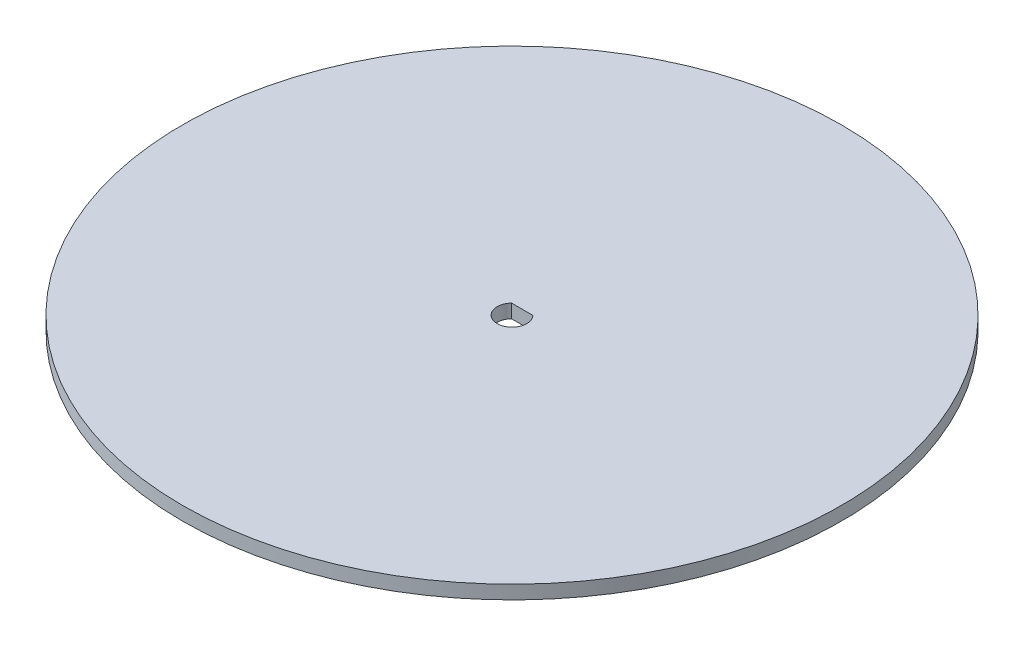
SolidWorks part; units mm, degrees
ref_plane "Front Plane" through (0, 0, 0) normal (0, 0, 1) x (1, 0, 0)
ref_plane "Top Plane" through (0, 0, 0) normal (0, 1, 0) x (1, 0, 0)
ref_plane "Right Plane" through (0, 0, 0) normal (1, 0, 0) x (0, 0, -1)
sketch "Sketch1" plane through (0, 0, 0) normal (0, 1, 0) x (1, 0, 0)
  circle A0 centre (0, 0) radius 72.5
  dimension "D1" = 145
base flange "Base-Flange1" sketch "Sketch1" thickness 3 reverse thickness direction no parameters "D1"=0.7366
sketch "Sketch6" plane through (0, 0, 0) normal (0, 1, 0) x (1, 0, 0)
  line L0 (-2.3452, 2.25) -> (2.3452, 2.25)
  circle A0 centre (0, 0) radius 3.25 construction
  arc A1 (-2.3452, 2.25) -> (2.3452, 2.25) centre (0, 0) ccw
  point P5 (0, -3.25)
  dimension "D1" = 6.5
  dimension "D2" = 5.5
extrude "Cut-Extrude1" cut sketch "Sketch6" against normal up to next normal cut yes
sketch "Bend-Lines1" [suppressed] plane through (0, 0, 0) normal (0, 1, 0) x (1, 0, 0)
sketch "Bounding-Box1" [suppressed] plane through (0, 0, 0) normal (0, 1, 0) x (1, 0, 0)
sheet metal parameters "Sheet-Metal1" thickness 3 parameters "D1"=0.7366
flat pattern "Flat-Pattern1" [suppressed]
sketch "Bend-Lines2" plane through (0, 0, 0) normal (0, 1, 0) x (1, 0, 0)
sketch3d "Bounding-Box2" [suppressed]
  line L0 (-72.5672, 72.4327, 0) -> (-72.4327, -72.5672, 0) construction
  line L1 (72.4327, 72.5672, 0) -> (72.5672, -72.4327, 0) construction
  line L2 (-72.5672, 72.4327, 0) -> (72.4327, 72.5672, 0) construction
  line L3 (-72.4327, -72.5672, 0) -> (72.5672, -72.4327, 0) construction
sheet metal parameters "Sheet-Metal2" thickness 3 parameters "D1"=0.7366
flat pattern "Flat-Pattern1"
sketch "Bend-Lines2" plane through (0, 0, 0) normal (0, 1, 0) x (1, 0, 0)
sketch3d "Bounding-Box2" [suppressed]
  line L0 (-72.5672, 72.4327, 0) -> (-72.4327, -72.5672, 0) construction
  line L1 (72.4327, 72.5672, 0) -> (72.5672, -72.4327, 0) construction
  line L2 (-72.5672, 72.4327, 0) -> (72.4327, 72.5672, 0) construction
  line L3 (-72.4327, -72.5672, 0) -> (72.5672, -72.4327, 0) construction
